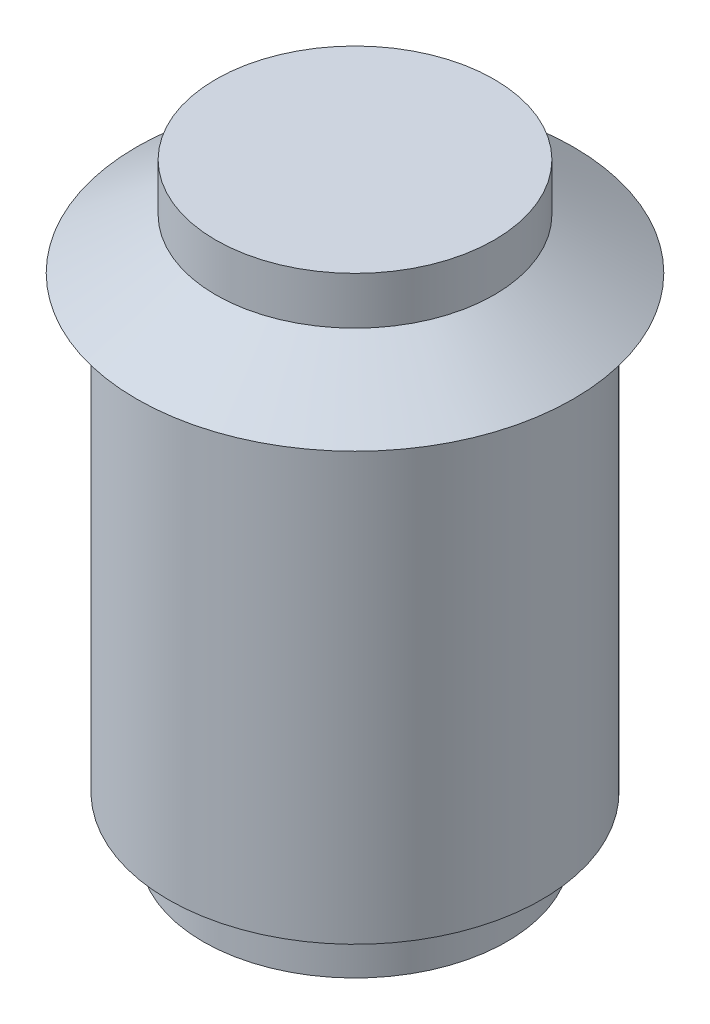
SolidWorks part; units mm, degrees
ref_plane "Front Plane" through (0, 0, 0) normal (0, 0, 1) x (1, 0, 0)
ref_plane "Top Plane" through (0, 0, 0) normal (0, 1, 0) x (1, 0, 0)
ref_plane "Right Plane" through (0, 0, 0) normal (1, 0, 0) x (0, 0, -1)
sketch "Sketch1" plane through (0, 0, 0) normal (1, 0, 0) x (0, 0, -1)
  line L0 (0, 0) -> (0, 25.0916) construction
  line L1 (0, 0) -> (0, 19)
  line L2 (0, 19) -> (4.4, 19)
  line L3 (4.4, 19) -> (4.4, 17.5)
  line L4 (4.4, 17.5) -> (6.9, 15.9)
  line L5 (6.9, 15.9) -> (5.9, 15.9)
  line L6 (5.9, 15.9) -> (5.9, 1.7)
  line L7 (5.9, 1.7) -> (4.8, 1.7)
  line L8 (4.8, 1.7) -> (4.8, 0)
  line L9 (4.8, 0) -> (0, 0)
  point P3 (4.8, 0.85)
  dimension "D1" = 19
  dimension "D2" = 8.8
  dimension "D3" = 1.5
  dimension "D4" = 13.8
  dimension "D5" = 1.6
  dimension "D6" = 11.8
  dimension "D7" = 9.6
  dimension "D8" = 1.7
revolve "Revolve1" add sketch "Sketch1" angle 360 about L0
